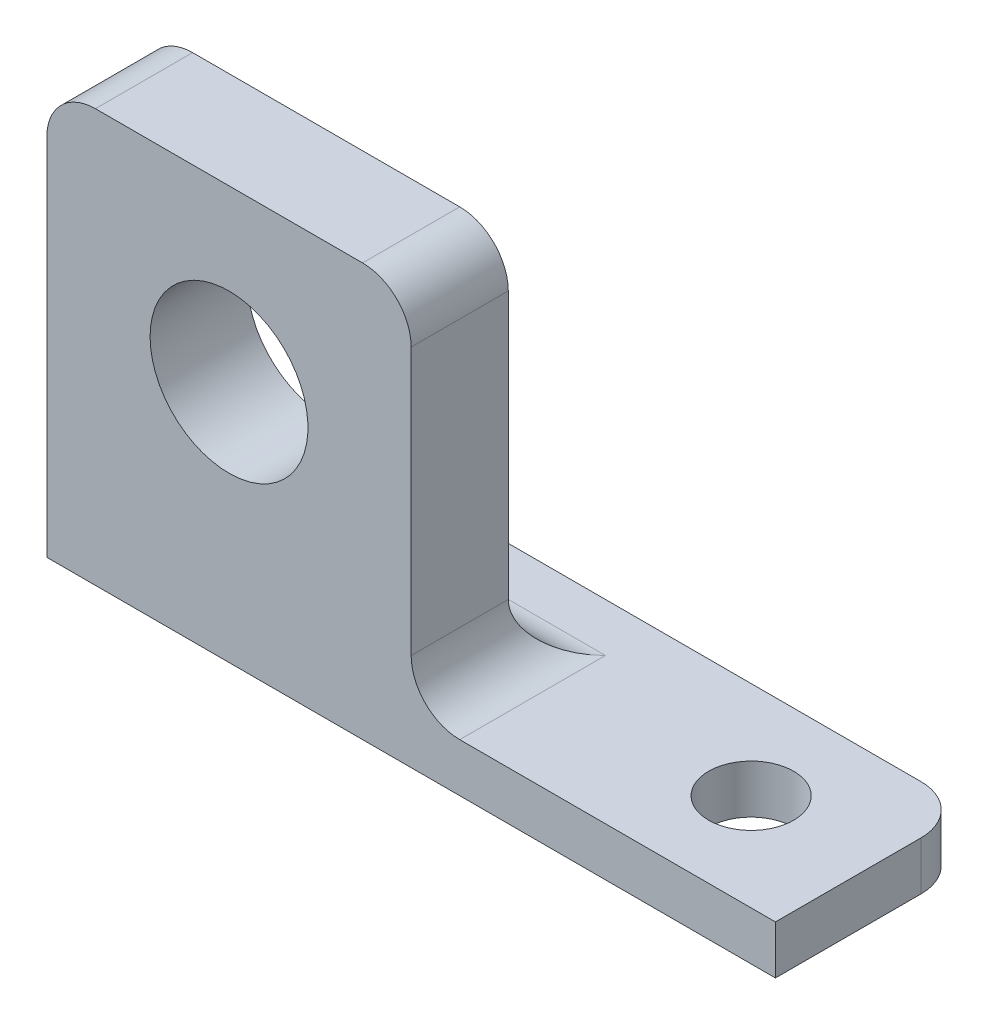
SolidWorks part; units mm, degrees
ref_plane "Alzado" through (0, 0, 0) normal (0, 0, 1) x (1, 0, 0)
ref_plane "Planta" through (0, 0, 0) normal (0, 1, 0) x (1, 0, 0)
ref_plane "Vista lateral" through (0, 0, 0) normal (1, 0, 0) x (0, 0, -1)
sketch "Croquis1" plane through (0, 0, 0) normal (0, 1, 0) x (1, 0, 0)
  line L0 (0, 4) -> (-30, 4) construction
  line L1 (0, 0) -> (-30, 0)
  line L2 (0, 0) -> (0, 8)
  line L3 (0, 8) -> (-30, 8)
  line L4 (-30, 0) -> (-30, 8)
  circle A0 centre (-5, 4) radius 1.75
  point P9 (0, 0)
  point P10 (-4.7983, 6)
  dimension "D2" = 3.5
  dimension "D1" = 8
  dimension "D3" = 5
  dimension "D4" = 30
extrude "Saliente-Extruir1" add sketch "Croquis1" along normal blind 2
sketch "Croquis2" plane through (0, 2, 0) normal (0, 1, 0) x (1, 0, 0)
  line L0 (-30, 8) -> (-30, 0) construction
  line L1 (-30, 4) -> (-15, 4)
  line L2 (-30, 4) -> (-30, 0)
  line L3 (-30, 0) -> (-15, 0)
  line L4 (-15, 4) -> (-15, 0)
  line L6 (-30, 0) -> (0, 0) construction
  dimension "5" = 4
  dimension "D2" = 15
extrude "Saliente-Extruir2" add sketch "Croquis2" along normal blind 15
sketch "Croquis3" plane through (0, 0, -4) normal (0, 0, -1) x (-1, 0, 0)
  line L0 (22.5, 17) -> (22.5, 2) construction
  line L1 (15, 17) -> (30, 17) construction
  line L2 (15, 2) -> (30, 2) construction
  circle A0 centre (22.5, 10) radius 3.25
  point P8 (22.5, 11.0997)
  dimension "D1" = 6.5
  dimension "D2" = 8
extrude "Cortar-Extruir1" cut sketch "Croquis3" against normal up to surface (4 mm away) up to face at (-15, 6.3333, 0)
fillet "Redondeo1" radius 2 6 edges at (0, 1, -8) (-30, 1, -8) (-30, 17, -2) (-15, 17, -2) (-22.5, 2, -4) (-15, 2, -2)
